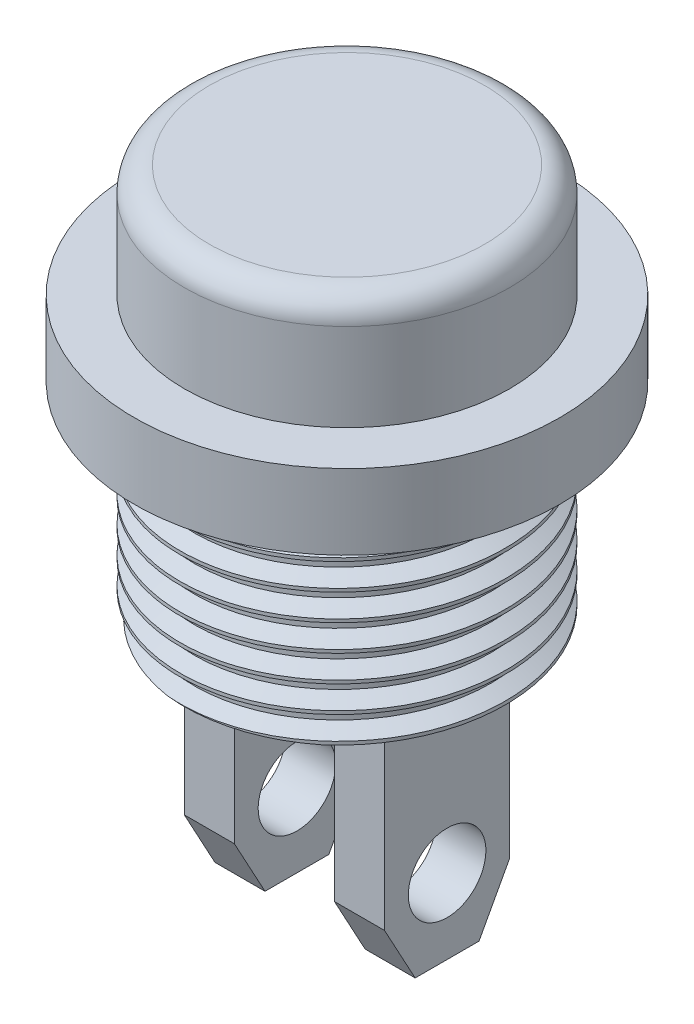
SolidWorks part; units mm, degrees
ref_plane "Plano frontal" through (0, 0, 0) normal (0, 0, 1) x (1, 0, 0)
ref_plane "Plano superior" through (0, 0, 0) normal (0, 1, 0) x (1, 0, 0)
ref_plane "Plano direito" through (0, 0, 0) normal (1, 0, 0) x (0, 0, -1)
sketch "Esboço1" plane through (0, 0, 0) normal (0, 0, 1) x (1, 0, 0)
  line L0 (6.5, 4.5) -> (6.5, -11)
  line L1 (6.5, 0) -> (13, 0)
  line L3 (6.5, 4.5) -> (12, 4.5)
  line L4 (13, 0) -> (13, 3.5)
  line L12 (15, 0) -> (15, -3)
  line L13 (6.5, -3) -> (13, -3)
  line L15 (6.5, -11) -> (13, -11)
  line L16 (13, -3) -> (13, -11)
  line L17 (6.5, 0) -> (15, 0)
  line L18 (6.5, -3) -> (15, -3)
  arc A0 (13, 3.5) -> (12, 4.5) centre (12, 3.5) ccw
  point P5 (6.1595, 4.347)
  point P11 (13, 4.5)
  point P14 (0, 4.5)
  dimension "D3" = 1
  dimension "D1" = 13
  dimension "D5" = 8.5
revolve "Revolução1" add sketch "Esboço1" angle 360 about L0 region at (9.7276, 2.235, 0) region at (10.75, -1.5, 0) region at (9.75, -7, 0)
sketch "Esboço2" plane through (0, -11, 0) normal (0, -1, 0) x (1, 0, 0)
  line L1 (2.5, 2.5) -> (4.5, 2.5)
  line L2 (2.5, 2.5) -> (2.5, -2.5)
  line L3 (2.5, -2.5) -> (4.5, -2.5)
  line L4 (4.5, 2.5) -> (4.5, -2.5)
  line L5 (8.5, 2.5) -> (10.5, 2.5)
  line L6 (8.5, 2.5) -> (8.5, -2.5)
  line L7 (8.5, -2.5) -> (10.5, -2.5)
  line L8 (10.5, 2.5) -> (10.5, -2.5)
  circle A0 centre (6.5, 0) radius 6.5 construction
  circle A1 centre (6.5, 0) radius 6.5 construction
  dimension "D1" = 2
  dimension "D2" = 5
  dimension "D3" = 2.5
  dimension "D4" = 4
  dimension "D5" = 2
  dimension "D6" = 4
extrude "Ressalto-extrusão1" add sketch "Esboço2" along normal blind 10
sketch "Esboço3" plane through (10.5, 0, 0) normal (1, 0, 0) x (0, 0, -1)
  line L0 (-2.5, -18.7426) -> (-1.2756, -21)
  line L1 (-2.5, -21) -> (-2.5, -11) construction
  line L2 (2.5, -21) -> (-2.5, -21) construction
  line L3 (2.5, -18.7426) -> (1.2756, -21)
  line L4 (2.5, -21) -> (2.5, -11) construction
  line L5 (-2.5, -18.7426) -> (-2.5, -21)
  line L6 (-2.5, -21) -> (-1.2756, -21)
  line L7 (1.2756, -21) -> (2.5, -21)
  line L8 (2.5, -21) -> (2.5, -18.7426)
  circle A0 centre (0, -18) radius 1.55
  dimension "D1" = 3.1
  dimension "D2" = 3
  dimension "D3" = 2.5
extrude "Corte-extrusão1" cut sketch "Esboço3" against normal blind 10
thread "Rosca1" pitch 1.0583 method cut profile "Perfil da rosca1" start angle 30, offset 0, length 8, pitch 1.0583, diameter 13
ref_plane "Plano1" through (0.8708, -3, -3.25) normal (-0.5, 0, 0.866) x (-0.866, 0, -0.5)
sketch "Perfil da rosca1" plane through (0.8708, -3, -3.25) normal (-0.5, 0, 0.866) x (-0.866, 0, -0.5)
  line L0 (0, 0) -> (0, 1.0583) construction
  line L11 (0, 0) -> (0, 0.926)
  line L12 (0, 0.926) -> (-0.5728, 0.5953)
  line L13 (-0.5728, 0.5953) -> (-0.5728, 0.3307)
  line L15 (-0.5728, 0.3307) -> (0, 0)
  line L17 (-0.5728, 0.463) -> (0, 0.463) construction
  point P2 (0, 0)
  dimension "Pitch" = 1.0583
  dimension "Profile_Angle" = 60
  dimension "Profile_Land" = 0.2646
  dimension "Profile_Height" = 0.5728
